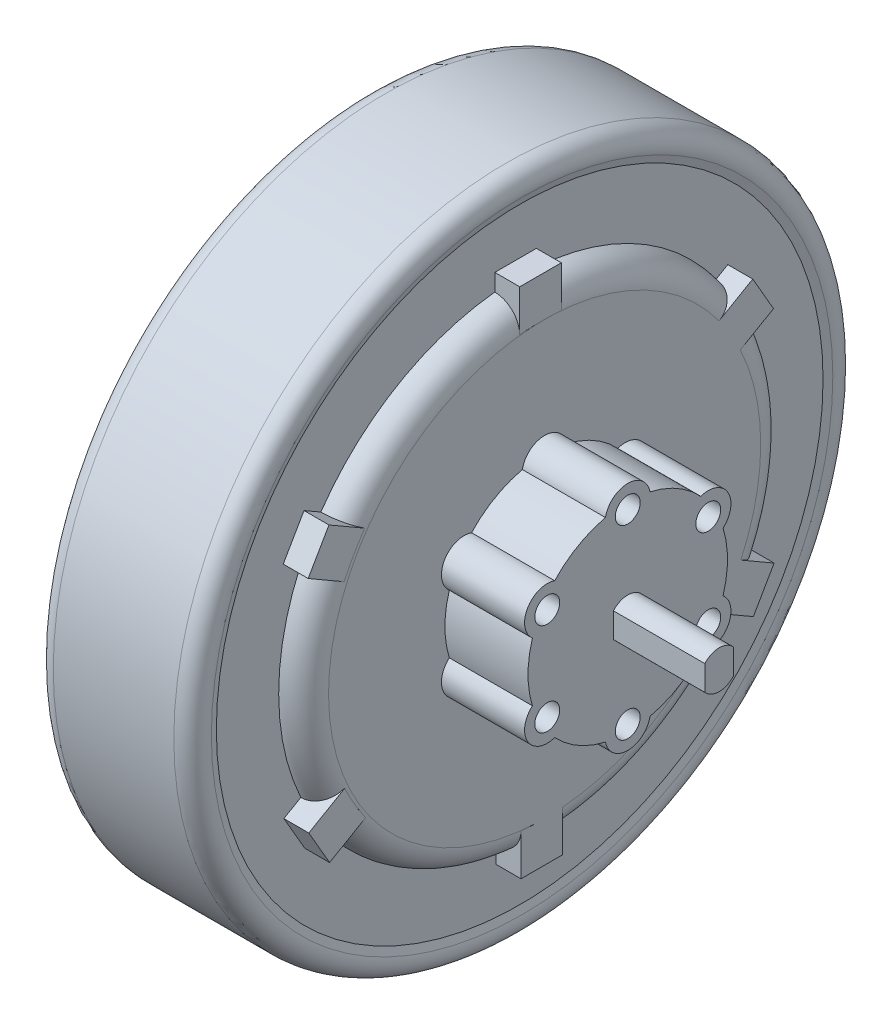
SolidWorks part; units mm, degrees
ref_plane "Front Plane" through (0, 0, 0) normal (0, 0, 1) x (1, 0, 0)
ref_plane "Top Plane" through (0, 0, 0) normal (0, 1, 0) x (1, 0, 0)
ref_plane "Right Plane" through (0, 0, 0) normal (1, 0, 0) x (0, 0, -1)
sketch "Sketch1" plane through (0, 0, 0) normal (0, 1, 0) x (1, 0, 0)
  line L0 (0, 0) -> (0, 89.9577) construction
  line L1 (-25.4, 89.9577) -> (25.4, 89.9577)
  line L2 (25.4, 89.9577) -> (22.528, 81.0677)
  line L3 (22.528, 81.0677) -> (22.528, 62.0177)
  line L4 (22.528, 62.0177) -> (30.148, 62.0177)
  line L5 (30.148, 62.0177) -> (30.148, 18.8377)
  line L6 (27.9161, -11.6423) -> (-27.9161, -11.6423)
  line L7 (0, -11.6423) -> (0, 89.9577)
  line L8 (30.148, 62.0177) -> (30.148, 68.7262) construction
  line L9 (30.148, 18.8377) -> (55.548, 18.8377)
  line L10 (55.548, 18.8377) -> (55.548, -11.6423)
  line L11 (55.548, -11.6423) -> (27.9161, -11.6423)
  line L12 (-30.148, 62.0177) -> (-30.148, 68.7262) construction
  line L13 (-30.148, -11.6423) -> (-27.9161, -11.6423)
  line L16 (-30.148, 62.0177) -> (-30.148, 18.8377)
  line L17 (-22.528, 62.0177) -> (-30.148, 62.0177)
  line L18 (-22.528, 81.0677) -> (-22.528, 62.0177)
  line L19 (-25.4, 89.9577) -> (-22.528, 81.0677)
  line L21 (-30.1884, -2.7523) -> (-36.5384, -2.7523)
  line L22 (-36.5384, -2.7523) -> (-36.5384, -4.5696)
  line L23 (-36.5384, -11.6423) -> (-30.148, -11.6423)
  line L24 (-30.1884, -2.7523) -> (-30.148, 18.8377)
  line L25 (-36.5384, -4.5696) -> (-38.4853, -4.5696)
  line L26 (-38.4853, -4.5696) -> (-38.4853, -11.6423)
  line L27 (-38.4853, -11.6423) -> (-36.5384, -11.6423)
  dimension "D1" = 101.6
  dimension "D2" = 8.89
  dimension "D3" = 19.05
  dimension "D4" = 7.62
  dimension "D5" = 90
  dimension "D6" = 25.4
  dimension "D7" = 6.35
  dimension "D8" = 25.4
  dimension "D9" = 71.12
  dimension "D10" = 8.89
revolve "Revolve1" add sketch "Sketch1" angle 360 about L6
ref_plane "Plane1" through (55.548, 0, 0) normal (1, 0, 0) x (0, 0, -1)
fillet "Fillet1" radius 7.62 2 edges at (30.148, 0, -62.0177) (-30.148, 0, -62.0177)
ref_plane "Plane2" through (-30.148, 0, 0) normal (-1, 0, 0) x (0, 0, 1)
sketch "Sketch3" plane through (-30.148, 0, 0) normal (-1, 0, 0) x (0, 0, 1)
  line L0 (6.5481, 65.8481) -> (6.5481, 78.4819)
  line L1 (6.5481, 78.4819) -> (19.2481, 78.4819)
  line L2 (19.2481, 78.4819) -> (19.2481, 65.7819)
  line L3 (12.8981, 30.4541) -> (12.8981, 78.4819) construction
  line L4 (83.9057, 33.5987) -> (72.9072, 27.2487)
  line L5 (77.5557, 44.5973) -> (83.9057, 33.5987)
  line L6 (66.6145, 38.2803) -> (77.5557, 44.5973)
  line L7 (77.3646, -44.838) -> (66.366, -38.488)
  line L8 (83.7146, -33.8395) -> (77.3646, -44.838)
  line L9 (72.7734, -27.5226) -> (83.7146, -33.8395)
  line L10 (6.1658, -78.3916) -> (6.1658, -65.6916)
  line L11 (18.8658, -78.3916) -> (6.1658, -78.3916)
  line L12 (18.8658, -65.7578) -> (18.8658, -78.3916)
  line L13 (-58.4919, -33.5084) -> (-47.4933, -27.1584)
  line L14 (-52.1419, -44.5069) -> (-58.4919, -33.5084)
  line L15 (-41.2006, -38.19) -> (-52.1419, -44.5069)
  line L16 (-51.9507, 44.9283) -> (-40.9522, 38.5783)
  line L17 (-58.3007, 33.9298) -> (-51.9507, 44.9283)
  line L18 (-47.3595, 27.6129) -> (-58.3007, 33.9298)
  circle A0 centre (11.6423, 0) radius 66.04 construction
  circle A1 centre (11.6423, 0) radius 30.48 construction
  circle A2 centre (11.6423, 0) radius 30.48 construction
  arc A3 (6.5481, 65.8481) -> (19.2481, 65.7819) centre (12.5157, -7.5698) cw
  arc A4 (66.6145, 38.2803) -> (72.9072, 27.2487) centre (6.0166, -3.5967) cw
  arc A5 (72.7734, -27.5226) -> (66.366, -38.488) centre (6.2078, 4.0183) cw
  arc A6 (18.8658, -65.7578) -> (6.1658, -65.6916) centre (12.8982, 7.6601) cw
  arc A7 (-41.2006, -38.19) -> (-47.4933, -27.1584) centre (19.3973, 3.687) cw
  arc A8 (-47.3595, 27.6129) -> (-40.9522, 38.5783) centre (19.206, -3.9279) cw
  point P41 (12.7069, 0.0452)
  dimension "D1" = 12.7
  dimension "D2" = 12.7
  dimension "D3" = 6
extrude "Boss-Extrude1" add sketch "Sketch3" against normal up to next
ref_plane "Plane3" through (0, 10.8699, 6.2757) normal (0, 0.866, 0.5) x (1, 0, 0)
sketch "Sketch5" plane through (0, 10.8699, 6.2757) normal (0, 0.866, 0.5) x (1, 0, 0)
  line L0 (-55.548, -10.0826) -> (-84.4313, -10.0826) construction
  line L1 (-55.548, 20.3974) -> (-55.548, -40.5626) construction
  line L2 (-30.4898, -79.7792) -> (-23.3898, -90.3477)
  line L5 (-23.3898, -90.3477) -> (-30.4898, -90.3477)
  line L6 (-30.4898, -90.3477) -> (-30.4898, -79.7792)
mirror "Mirror1" about plane through (0, 0, 0) normal (1, 0, 0) of "Boss-Extrude1"
sketch "Sketch7" plane through (55.548, 0, 0) normal (1, 0, 0) x (0, 0, -1)
  arc A0 (-18.451, 29.7098) -> (-4.8337, 29.7098) centre (-11.6423, 28.4042) cw
  circle A1 centre (-11.6423, 0) radius 30.48 construction
  arc A2 (-18.451, 29.7098) -> (-4.8337, 29.7098) centre (-11.6423, 0) cw
  arc A3 (10.6828, 20.7514) -> (17.4914, 8.9584) centre (-11.6423, 0) cw
  arc A4 (10.6828, 20.7514) -> (17.4914, 8.9584) centre (12.9564, 14.2021) cw
  arc A5 (17.4914, -8.9584) -> (10.6828, -20.7514) centre (-11.6423, 0) cw
  arc A6 (17.4914, -8.9584) -> (10.6828, -20.7514) centre (12.9564, -14.2021) cw
  arc A7 (-4.8337, -29.7098) -> (-18.451, -29.7098) centre (-11.6423, 0) cw
  arc A8 (-4.8337, -29.7098) -> (-18.451, -29.7098) centre (-11.6423, -28.4042) cw
  arc A9 (-33.9675, -20.7514) -> (-40.7761, -8.9584) centre (-11.6423, 0) cw
  arc A10 (-33.9675, -20.7514) -> (-40.7761, -8.9584) centre (-36.2411, -14.2021) cw
  arc A11 (-40.7761, 8.9584) -> (-33.9675, 20.7514) centre (-11.6423, 0) cw
  arc A12 (-40.7761, 8.9584) -> (-33.9675, 20.7514) centre (-36.2411, 14.2021) cw
  point P24 (-11.6423, 0)
  dimension "D1" = 6
extrude "Boss-Extrude2" add sketch "Sketch7" against normal up to next
sketch "Sketch8" plane through (55.548, 0, 0) normal (1, 0, 0) x (0, 0, -1)
  circle A0 centre (-11.6423, 28.4042) radius 3.81
  circle A1 centre (12.9564, 14.2021) radius 3.81
  circle A2 centre (12.9564, -14.2021) radius 3.81
  circle A3 centre (-11.6423, -28.4042) radius 3.81
  circle A4 centre (-36.2411, -14.2021) radius 3.81
  circle A5 centre (-36.2411, 14.2021) radius 3.81
  point P16 (-11.6423, 0)
  dimension "D1" = 6
extrude "Cut-Extrude1" cut sketch "Sketch8" against normal blind 10.16
sketch "Sketch9" plane through (55.548, 0, 0) normal (1, 0, 0) x (0, 0, -1)
  line L0 (-7.2635, 3.8093) -> (-7.2635, -3.8093)
  line L1 (-11.6423, 0) -> (-11.6423, 3.5304) construction
  line L2 (-16.0212, 3.8093) -> (-16.0212, -3.8093)
  arc A0 (-16.0212, -3.8093) -> (-7.2635, -3.8093) centre (-11.6423, 0) ccw
  arc A1 (-7.2635, 3.8093) -> (-16.0212, 3.8093) centre (-11.6423, 0) ccw
  point P1 (-11.6423, 0.925)
  dimension "D1" = 11.6078
extrude "Boss-Extrude3" add sketch "Sketch9" along normal blind 58.42 from offset 30.48 offset against normal yes
mirror "Mirror3" about plane through (0, 0, 0) normal (1, 0, 0) of "Boss-Extrude3"
fillet "Fillet2" radius 5.08 2 edges at (-25.4, 0, -89.9577) (25.4, 0, -89.9577)
sketch "Sketch10" plane through (0, 0, 0) normal (0, 0, 1) x (1, 0, 0)
  line L1 (-86.9993, 14.1566) -> (-59.5673, 14.1566)
  line L2 (-86.9993, 14.1566) -> (-86.9993, -9.7028)
  line L3 (-86.9993, -9.7028) -> (-59.5673, -9.7028)
  line L4 (-59.5673, 14.1566) -> (-59.5673, -9.7028)
  line L5 (-86.9993, 14.1566) -> (-59.5673, -9.7028) construction
  line L6 (-86.9993, -9.7028) -> (-59.5673, 14.1566) construction
  point P4 (-73.2833, 2.2269)
  dimension "D1" = 27.432
extrude "Cut-Extrude2" cut sketch "Sketch10" against normal through all both and the other way through all
